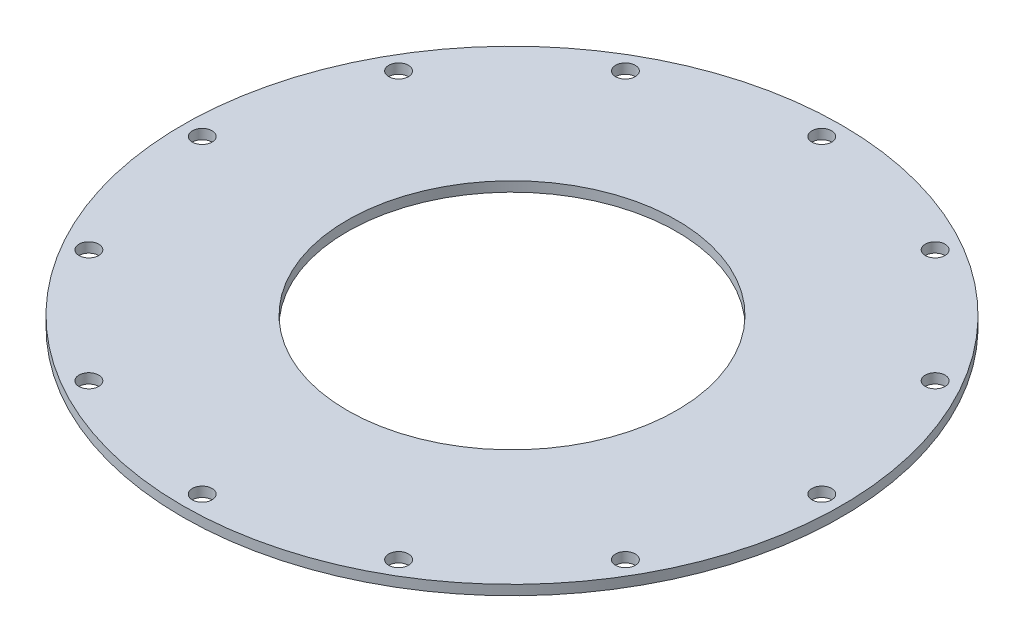
SolidWorks part; units mm, degrees
material "Thornel Mat VMA"
ref_plane "Front Plane" through (0, 0, 0) normal (0, 0, 1) x (1, 0, 0)
ref_plane "Top Plane" through (0, 0, 0) normal (0, 1, 0) x (1, 0, 0)
ref_plane "Right Plane" through (0, 0, 0) normal (1, 0, 0) x (0, 0, -1)
sketch "Sketch1" plane through (0, 0, 0) normal (0, 1, 0) x (1, 0, 0)
  circle A0 centre (0, 0) radius 50
  circle A1 centre (0, 0) radius 100
  dimension "D1" = 100
  dimension "D2" = 200
extrude "Base" add sketch "Sketch1" along normal mid plane 3
sketch "Sketch2" plane through (0, 1.5, 0) normal (0, 1, 0) x (1, 0, 0)
  line L0 (0, 97) -> (0, 100) construction
  circle A0 centre (0, 94) radius 3
  circle A1 centre (0, 0) radius 100 construction
  dimension "D1" = 6
  dimension "D2" = 3
extrude "Structural Hole" cut sketch "Sketch2" against normal through all
pattern_circular "Structural Hole Pattern" count 6 over 360 about axis through (0, 1.5, 0) along (0, -1, 0) of "Structural Hole" reverse direction yes
sketch "Sketch3" plane through (0, 1.5, 0) normal (0, 1, 0) x (1, 0, 0)
  line L0 (47, 81.4064) -> (0, 0) construction
  line L1 (0, 0) -> (0, 46.5025) construction
  line L2 (50, 86.6025) -> (48.5, 84.0045) construction
  circle A0 centre (47, 81.4064) radius 3
  circle A1 centre (0, 0) radius 100 construction
  dimension "D2" = 6
  dimension "D1" = 30
  dimension "D3" = 3
extrude "Bearing Hole" cut sketch "Sketch3" against normal through all
pattern_circular "Bearing Hole Pattern" count 6 over 360 about axis through (0, 1.5, 0) along (0, -1, 0) of "Bearing Hole" reverse direction yes
equation "\"lift_fan_diameter\"=100"
equation "\"D1@Sketch1\"=\"lift_fan_diameter\""
equation "\"outer_diameter\"=200"
equation "\"D2@Sketch1\"=\"outer_diameter\""
equation "\"bolt_diameter\"=6"
equation "\"D1@Sketch2\"=\"bolt_diameter\""
equation "\"wall_thickness\"=3"
equation "\"D2@Sketch2\"=\"wall_thickness\""
equation "\"D2@Sketch3\"=\"bolt_diameter\""
equation "\"D3@Sketch3\"=\"wall_thickness\""
